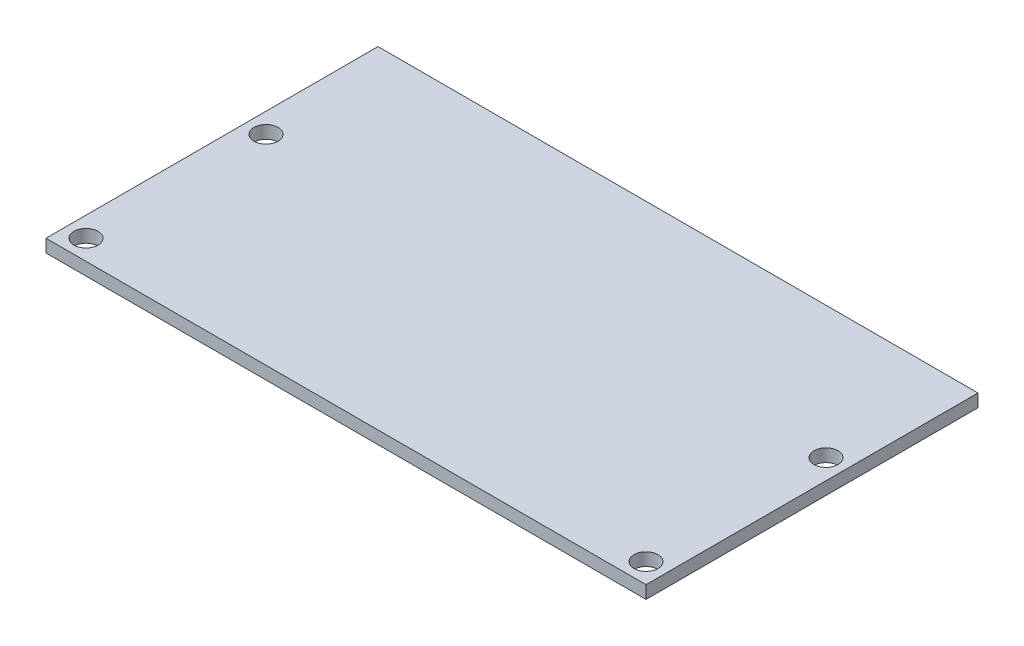
SolidWorks part; units mm, degrees
ref_plane "Front Plane" through (0, 0, 0) normal (0, 0, 1) x (1, 0, 0)
ref_plane "Top Plane" through (0, 0, 0) normal (0, 1, 0) x (1, 0, 0)
ref_plane "Right Plane" through (0, 0, 0) normal (1, 0, 0) x (0, 0, -1)
sketch "Sketch1" plane through (0, 0, 0) normal (0, 1, 0) x (1, 0, 0)
  line L1 (0, 0) -> (75, 0)
  line L2 (0, 0) -> (0, 41.5)
  line L3 (0, 41.5) -> (75, 41.5)
  line L4 (75, 0) -> (75, 41.5)
  dimension "D1" = 75
  dimension "D2" = 41.5
extrude "Boss-Extrude1" add sketch "Sketch1" along normal blind 1.6
sketch "Sketch2" plane through (0, 0, 0) normal (0, -1, 0) x (1, 0, 0)
  line L0 (0, 0) -> (75, 0) construction
  line L1 (0, -41.5) -> (0, 0) construction
  line L2 (75, 0) -> (75, -41.5) construction
  circle A0 centre (2.5, -2.5) radius 1.5
  circle A1 centre (72.5, -2.5) radius 1.5
  circle A2 centre (72.5, -25) radius 1.5
  circle A3 centre (2.5, -25) radius 1.5
  point P16 (75, -1.2659)
  dimension "D1" = 3
  dimension "D2" = 3
  dimension "D3" = 3
  dimension "D4" = 3
  dimension "D5" = 2.5
  dimension "D6" = 2.5
  dimension "D7" = 2.5
  dimension "D8" = 2.5
  dimension "D9" = 2.5
  dimension "D10" = 25
  dimension "D11" = 2.5
  dimension "D12" = 25
extrude "Cut-Extrude1" cut sketch "Sketch2" against normal blind 1.6
